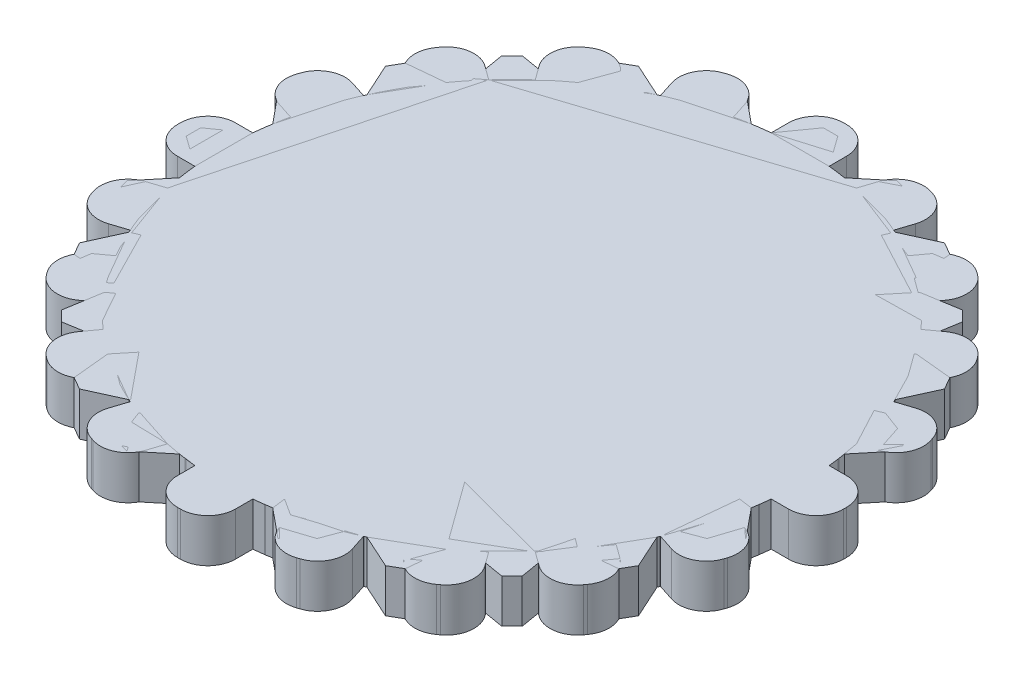
SolidWorks part; units mm, degrees
ref_plane "Front Plane" through (0, 0, 0) normal (0, 0, 1) x (1, 0, 0)
ref_plane "Top Plane" through (0, 0, 0) normal (0, 1, 0) x (1, 0, 0)
ref_plane "Right Plane" through (0, 0, 0) normal (1, 0, 0) x (0, 0, -1)
sketch "Sketch1" plane through (0, 0, 0) normal (0, 1, 0) x (1, 0, 0)
  line L111 (-0.5, 14.7462) -> (0.5, 14.7462)
  line L112 (0.5, 14.7462) -> (2, 12.5441)
  line L113 (-0.5, 14.7462) -> (-2, 12.5441)
  line L114 (6.433, 12.8885) -> (6.631, 10.2315)
  line L115 (5.567, 13.3885) -> (6.433, 12.8885)
  line L116 (5.567, 13.3885) -> (3.1669, 12.2315)
  line L117 (10.6423, 8.3132) -> (9.4853, 5.9131)
  line L118 (10.1423, 9.1792) -> (10.6423, 8.3132)
  line L119 (10.1423, 9.1792) -> (7.4853, 9.3772)
  line L120 (12, 2.2462) -> (9.798, 0.7462)
  line L121 (12, 3.2462) -> (12, 2.2462)
  line L122 (12, 3.2462) -> (9.798, 4.7462)
  line L123 (10.1423, -3.6868) -> (7.4853, -3.8849)
  line L124 (10.6423, -2.8208) -> (10.1423, -3.6868)
  line L125 (10.6423, -2.8208) -> (9.4853, -0.4208)
  line L126 (5.567, -7.8961) -> (3.1669, -6.7391)
  line L127 (6.433, -7.3961) -> (5.567, -7.8961)
  line L128 (6.433, -7.3961) -> (6.631, -4.7391)
  line L129 (-0.5, -9.2538) -> (-2, -7.0518)
  line L130 (0.5, -9.2538) -> (-0.5, -9.2538)
  line L131 (0.5, -9.2538) -> (2, -7.0518)
  line L132 (-6.433, -7.3961) -> (-6.631, -4.7391)
  line L133 (-5.567, -7.8961) -> (-6.433, -7.3961)
  line L134 (-5.567, -7.8961) -> (-3.1669, -6.7391)
  line L135 (-10.6423, -2.8208) -> (-9.4853, -0.4208)
  line L136 (-10.1423, -3.6868) -> (-10.6423, -2.8208)
  line L137 (-10.1423, -3.6868) -> (-7.4853, -3.8849)
  line L138 (-12, 3.2462) -> (-9.798, 4.7462)
  line L139 (-12, 2.2462) -> (-12, 3.2462)
  line L140 (-12, 2.2462) -> (-9.798, 0.7462)
  line L141 (-10.1423, 9.1792) -> (-7.4853, 9.3772)
  line L142 (-10.6423, 8.3132) -> (-10.1423, 9.1792)
  line L143 (-10.6423, 8.3132) -> (-9.4853, 5.9131)
  line L144 (-5.567, 13.3885) -> (-3.1669, 12.2315)
  line L145 (-6.433, 12.8885) -> (-5.567, 13.3885)
  line L146 (-6.433, 12.8885) -> (-6.631, 10.2315)
  arc A43 (-2, 12.5441) -> (-3.1669, 12.2315) centre (0, 2.7462) ccw
  arc A44 (-6.631, 10.2315) -> (-7.4853, 9.3772) centre (0, 2.7462) ccw
  arc A45 (-9.4853, 5.9131) -> (-9.798, 4.7462) centre (0, 2.7462) ccw
  arc A46 (-9.798, 0.7462) -> (-9.4853, -0.4208) centre (0, 2.7462) ccw
  arc A47 (-7.4853, -3.8849) -> (-6.631, -4.7391) centre (0, 2.7462) ccw
  arc A48 (-3.1669, -6.7391) -> (-2, -7.0518) centre (0, 2.7462) ccw
  arc A49 (2, -7.0518) -> (3.1669, -6.7391) centre (0, 2.7462) ccw
  arc A50 (6.631, -4.7391) -> (7.4853, -3.8849) centre (0, 2.7462) ccw
  arc A51 (9.4853, -0.4208) -> (9.798, 0.7462) centre (0, 2.7462) ccw
  arc A52 (9.798, 4.7462) -> (9.4853, 5.9131) centre (0, 2.7462) ccw
  arc A53 (7.4853, 9.3772) -> (6.631, 10.2315) centre (0, 2.7462) ccw
  arc A54 (3.1669, 12.2315) -> (2, 12.5441) centre (0, 2.7462) ccw
  point P6 (0, 0)
  point P8 (0, 0)
  point P9 (0, 0)
  point P12 (0, 2.7462)
  point P17 (0, 0)
  point P18 (0, 2.7462)
  point P22 (-2.5, 0.7462)
  point P63 (0, 0)
  point P68 (0, 0)
  point P69 (0, 2.7462)
  point P119 (0, 0)
  dimension "D1" = 20
  dimension "D8" = 12
sketch "Sketch2" plane through (0, 0, 0) normal (0, 1, 0) x (1, 0, 0)
  line L0 (-2, 0) -> (2, 0)
  line L1 (-23, -0.1) -> (-23, 0.1)
  line L2 (-21.1, 2) -> (-19.8997, 2)
  line L3 (-21.1, -2) -> (-19.8997, -2)
  line L4 (-20.6853, 4.6181) -> (-19.5438, 4.2472)
  line L5 (-19.4493, 8.4224) -> (-18.3078, 8.0515)
  line L6 (-21.9052, 7.0123) -> (-21.8434, 7.2025)
  line L7 (-18.2458, 10.7842) -> (-17.2748, 10.0787)
  line L8 (-15.8947, 14.0203) -> (-14.9237, 13.3148)
  line L9 (-18.6662, 13.4382) -> (-18.5486, 13.6)
  line L10 (-14.0203, 15.8947) -> (-13.3148, 14.9237)
  line L11 (-10.7842, 18.2458) -> (-10.0787, 17.2748)
  line L12 (-13.6, 18.5486) -> (-13.4382, 18.6662)
  line L13 (-8.4224, 19.4493) -> (-8.0515, 18.3078)
  line L14 (-4.6181, 20.6853) -> (-4.2472, 19.5438)
  line L15 (-7.2025, 21.8434) -> (-7.0123, 21.9052)
  line L16 (-2, 21.1) -> (-2, 19.8997)
  line L17 (2, 21.1) -> (2, 19.8997)
  line L18 (-0.1, 23) -> (0.1, 23)
  line L19 (4.6181, 20.6853) -> (4.2472, 19.5438)
  line L20 (8.4224, 19.4493) -> (8.0515, 18.3078)
  line L21 (7.0123, 21.9052) -> (7.2025, 21.8434)
  line L22 (10.7842, 18.2458) -> (10.0787, 17.2748)
  line L23 (14.0203, 15.8947) -> (13.3148, 14.9237)
  line L24 (13.4382, 18.6662) -> (13.6, 18.5486)
  line L25 (15.8947, 14.0203) -> (14.9237, 13.3148)
  line L26 (18.2458, 10.7842) -> (17.2748, 10.0787)
  line L27 (18.5486, 13.6) -> (18.6662, 13.4382)
  line L28 (19.4493, 8.4224) -> (18.3078, 8.0515)
  line L29 (20.6853, 4.6181) -> (19.5438, 4.2472)
  line L30 (21.8434, 7.2025) -> (21.9052, 7.0123)
  line L31 (21.1, 2) -> (19.8997, 2)
  line L32 (21.1, -2) -> (19.8997, -2)
  line L33 (23, 0.1) -> (23, -0.1)
  line L34 (20.6853, -4.6181) -> (19.5438, -4.2472)
  line L35 (19.4493, -8.4224) -> (18.3078, -8.0515)
  line L36 (21.9052, -7.0123) -> (21.8434, -7.2025)
  line L37 (18.2458, -10.7842) -> (17.2748, -10.0787)
  line L38 (15.8947, -14.0203) -> (14.9237, -13.3148)
  line L39 (18.6662, -13.4382) -> (18.5486, -13.6)
  line L40 (14.0203, -15.8947) -> (13.3148, -14.9237)
  line L41 (10.7842, -18.2458) -> (10.0787, -17.2748)
  line L42 (13.6, -18.5486) -> (13.4382, -18.6662)
  line L43 (8.4224, -19.4493) -> (8.0515, -18.3078)
  line L44 (4.6181, -20.6853) -> (4.2472, -19.5438)
  line L45 (7.2025, -21.8434) -> (7.0123, -21.9052)
  line L46 (2, -21.1) -> (2, -19.8997)
  line L47 (-2, -21.1) -> (-2, -19.8997)
  line L48 (0.1, -23) -> (-0.1, -23)
  line L49 (-4.6181, -20.6853) -> (-4.2472, -19.5438)
  line L50 (-8.4224, -19.4493) -> (-8.0515, -18.3078)
  line L51 (-7.0123, -21.9052) -> (-7.2025, -21.8434)
  line L52 (-10.7842, -18.2458) -> (-10.0787, -17.2748)
  line L53 (-14.0203, -15.8947) -> (-13.3148, -14.9237)
  line L54 (-13.4382, -18.6662) -> (-13.6, -18.5486)
  line L55 (-15.8947, -14.0203) -> (-14.9237, -13.3148)
  line L56 (-18.2458, -10.7842) -> (-17.2748, -10.0787)
  line L57 (-18.5486, -13.6) -> (-18.6662, -13.4382)
  line L58 (-19.4493, -8.4224) -> (-18.3078, -8.0515)
  line L59 (-20.6853, -4.6181) -> (-19.5438, -4.2472)
  line L60 (-21.8434, -7.2025) -> (-21.9052, -7.0123)
  arc A0 (-18.3078, -8.0515) -> (-17.2748, -10.0787) centre (0, 0) ccw
  arc A1 (-21.1, 2) -> (-23, 0.1) centre (-21.1, 0.1) ccw
  arc A2 (-21.1, -2) -> (-23, -0.1) centre (-21.1, -0.1) cw
  arc A3 (-20.6853, 4.6181) -> (-21.9052, 7.0123) centre (-20.0982, 6.4252) cw
  arc A4 (-19.4493, 8.4224) -> (-21.8434, 7.2025) centre (-20.0364, 6.6154) ccw
  arc A5 (-18.2458, 10.7842) -> (-18.6662, 13.4382) centre (-17.129, 12.3214) cw
  arc A6 (-15.8947, 14.0203) -> (-18.5486, 13.6) centre (-17.0115, 12.4832) ccw
  arc A7 (-14.0203, 15.8947) -> (-13.6, 18.5486) centre (-12.4832, 17.0115) cw
  arc A8 (-10.7842, 18.2458) -> (-13.4382, 18.6662) centre (-12.3214, 17.129) ccw
  arc A9 (-8.4224, 19.4493) -> (-7.2025, 21.8434) centre (-6.6154, 20.0364) cw
  arc A10 (-4.6181, 20.6853) -> (-7.0123, 21.9052) centre (-6.4252, 20.0982) ccw
  arc A11 (-2, 21.1) -> (-0.1, 23) centre (-0.1, 21.1) cw
  arc A12 (2, 21.1) -> (0.1, 23) centre (0.1, 21.1) ccw
  arc A13 (4.6181, 20.6853) -> (7.0123, 21.9052) centre (6.4252, 20.0982) cw
  arc A14 (8.4224, 19.4493) -> (7.2025, 21.8434) centre (6.6154, 20.0364) ccw
  arc A15 (10.7842, 18.2458) -> (13.4382, 18.6662) centre (12.3214, 17.129) cw
  arc A16 (14.0203, 15.8947) -> (13.6, 18.5486) centre (12.4832, 17.0115) ccw
  arc A17 (15.8947, 14.0203) -> (18.5486, 13.6) centre (17.0115, 12.4832) cw
  arc A18 (18.2458, 10.7842) -> (18.6662, 13.4382) centre (17.129, 12.3214) ccw
  arc A19 (19.4493, 8.4224) -> (21.8434, 7.2025) centre (20.0364, 6.6154) cw
  arc A20 (20.6853, 4.6181) -> (21.9052, 7.0123) centre (20.0982, 6.4252) ccw
  arc A21 (21.1, 2) -> (23, 0.1) centre (21.1, 0.1) cw
  arc A22 (21.1, -2) -> (23, -0.1) centre (21.1, -0.1) ccw
  arc A23 (20.6853, -4.6181) -> (21.9052, -7.0123) centre (20.0982, -6.4252) cw
  arc A24 (19.4493, -8.4224) -> (21.8434, -7.2025) centre (20.0364, -6.6154) ccw
  arc A25 (18.2458, -10.7842) -> (18.6662, -13.4382) centre (17.129, -12.3214) cw
  arc A26 (15.8947, -14.0203) -> (18.5486, -13.6) centre (17.0115, -12.4832) ccw
  arc A27 (14.0203, -15.8947) -> (13.6, -18.5486) centre (12.4832, -17.0115) cw
  arc A28 (10.7842, -18.2458) -> (13.4382, -18.6662) centre (12.3214, -17.129) ccw
  arc A29 (8.4224, -19.4493) -> (7.2025, -21.8434) centre (6.6154, -20.0364) cw
  arc A30 (4.6181, -20.6853) -> (7.0123, -21.9052) centre (6.4252, -20.0982) ccw
  arc A31 (2, -21.1) -> (0.1, -23) centre (0.1, -21.1) cw
  arc A32 (-2, -21.1) -> (-0.1, -23) centre (-0.1, -21.1) ccw
  arc A33 (-4.6181, -20.6853) -> (-7.0123, -21.9052) centre (-6.4252, -20.0982) cw
  arc A34 (-8.4224, -19.4493) -> (-7.2025, -21.8434) centre (-6.6154, -20.0364) ccw
  arc A35 (-10.7842, -18.2458) -> (-13.4382, -18.6662) centre (-12.3214, -17.129) cw
  arc A36 (-14.0203, -15.8947) -> (-13.6, -18.5486) centre (-12.4832, -17.0115) ccw
  arc A37 (-15.8947, -14.0203) -> (-18.5486, -13.6) centre (-17.0115, -12.4832) cw
  arc A38 (-18.2458, -10.7842) -> (-18.6662, -13.4382) centre (-17.129, -12.3214) ccw
  arc A39 (-19.4493, -8.4224) -> (-21.8434, -7.2025) centre (-20.0364, -6.6154) cw
  arc A40 (-20.6853, -4.6181) -> (-21.9052, -7.0123) centre (-20.0982, -6.4252) ccw
  arc A41 (-19.8997, -2) -> (-19.5438, -4.2472) centre (0, 0) ccw
  arc A42 (-19.5438, 4.2472) -> (-19.8997, 2) centre (0, 0) ccw
  arc A43 (-17.2748, 10.0787) -> (-18.3078, 8.0515) centre (0, 0) ccw
  arc A44 (-13.3148, 14.9237) -> (-14.9237, 13.3148) centre (0, 0) ccw
  arc A45 (-8.0515, 18.3078) -> (-10.0787, 17.2748) centre (0, 0) ccw
  arc A46 (-2, 19.8997) -> (-4.2472, 19.5438) centre (0, 0) ccw
  arc A47 (4.2472, 19.5438) -> (2, 19.8997) centre (0, 0) ccw
  arc A48 (10.0787, 17.2748) -> (8.0515, 18.3078) centre (0, 0) ccw
  arc A49 (14.9237, 13.3148) -> (13.3148, 14.9237) centre (0, 0) ccw
  arc A50 (18.3078, 8.0515) -> (17.2748, 10.0787) centre (0, 0) ccw
  arc A51 (19.8997, 2) -> (19.5438, 4.2472) centre (0, 0) ccw
  arc A52 (19.5438, -4.2472) -> (19.8997, -2) centre (0, 0) ccw
  arc A53 (17.2748, -10.0787) -> (18.3078, -8.0515) centre (0, 0) ccw
  arc A54 (13.3148, -14.9237) -> (14.9237, -13.3148) centre (0, 0) ccw
  arc A55 (8.0515, -18.3078) -> (10.0787, -17.2748) centre (0, 0) ccw
  arc A56 (2, -19.8997) -> (4.2472, -19.5438) centre (0, 0) ccw
  arc A57 (-10.0787, -17.2748) -> (-8.0515, -18.3078) centre (0, 0) ccw
  arc A58 (-4.2472, -19.5438) -> (-2, -19.8997) centre (0, 0) ccw
  arc A59 (-14.9237, -13.3148) -> (-13.3148, -14.9237) centre (0, 0) ccw
  point P6 (0, 0)
  point P10 (-23, 2)
  point P170 (0, 0)
  dimension "D1" = 40
  dimension "D4" = 1.9
  dimension "D5" = 20
extrude "Boss-Extrude3" add sketch "Sketch2" along normal blind 3 contours L55 A59 L53 A36 L54 A35 L52 A57 L50 A34 L51 A33 L49 A58 L47 A32 L48 A31 L46 A56 L44 A30 L45 A29 L43 A55 L41 A28 L42 A27 L40 A54 L38 A26 L39 A25 L37 A53 L35 A24 L36 A23 L34 A52 L32 A22 L33 A21 region at (-22.3495, 0, 0)
sketch "Sketch3" plane through (0, 0, 0) normal (0, 1, 0) x (1, 0, 0)
  line L0 (-22, 0) -> (22, 0)
  line L1 (22, -0.5) -> (22, 0.5)
  line L2 (22, 0.5) -> (19.8997, 2)
  line L3 (22, -0.5) -> (19.8997, -2)
  line L4 (21.3798, -5.2111) -> (19.7393, -3.2186)
  line L5 (21.121, -6.177) -> (21.3798, -5.2111)
  line L6 (21.121, -6.177) -> (18.704, -7.0823)
  line L7 (19.3026, -10.567) -> (18.2337, -8.2178)
  line L8 (18.8026, -11.433) -> (19.3026, -10.567)
  line L9 (18.8026, -11.433) -> (16.2337, -11.6819)
  line L10 (15.9099, -15.2028) -> (15.4855, -12.657)
  line L11 (15.2028, -15.9099) -> (15.9099, -15.2028)
  line L12 (15.2028, -15.9099) -> (12.657, -15.4855)
  line L13 (11.433, -18.8026) -> (11.6819, -16.2337)
  line L14 (10.567, -19.3026) -> (11.433, -18.8026)
  line L15 (10.567, -19.3026) -> (8.2178, -18.2337)
  line L16 (6.177, -21.121) -> (7.0823, -18.704)
  line L17 (5.2111, -21.3798) -> (6.177, -21.121)
  line L18 (5.2111, -21.3798) -> (3.2186, -19.7393)
  line L19 (0.5, -22) -> (2, -19.8997)
  line L20 (-0.5, -22) -> (0.5, -22)
  line L21 (-0.5, -22) -> (-2, -19.8997)
  line L22 (-5.2111, -21.3798) -> (-3.2186, -19.7393)
  line L23 (-6.177, -21.121) -> (-5.2111, -21.3798)
  line L24 (-6.177, -21.121) -> (-7.0823, -18.704)
  line L25 (-10.567, -19.3026) -> (-8.2178, -18.2337)
  line L26 (-11.433, -18.8026) -> (-10.567, -19.3026)
  line L27 (-11.433, -18.8026) -> (-11.6819, -16.2337)
  line L28 (-15.2028, -15.9099) -> (-12.657, -15.4855)
  line L29 (-15.9099, -15.2028) -> (-15.2028, -15.9099)
  line L30 (-15.9099, -15.2028) -> (-15.4855, -12.657)
  line L31 (-18.8026, -11.433) -> (-16.2337, -11.6819)
  line L32 (-19.3026, -10.567) -> (-18.8026, -11.433)
  line L33 (-19.3026, -10.567) -> (-18.2337, -8.2178)
  line L34 (-21.121, -6.177) -> (-18.704, -7.0823)
  line L35 (-21.3798, -5.2111) -> (-21.121, -6.177)
  line L36 (-21.3798, -5.2111) -> (-19.7393, -3.2186)
  line L37 (-22, -0.5) -> (-19.8997, -2)
  line L38 (-22, 0.5) -> (-22, -0.5)
  line L39 (-22, 0.5) -> (-19.8997, 2)
  line L40 (-21.3798, 5.2111) -> (-19.7393, 3.2186)
  line L41 (-21.121, 6.177) -> (-21.3798, 5.2111)
  line L42 (-21.121, 6.177) -> (-18.704, 7.0823)
  line L43 (-19.3026, 10.567) -> (-18.2337, 8.2178)
  line L44 (-18.8026, 11.433) -> (-19.3026, 10.567)
  line L45 (-18.8026, 11.433) -> (-16.2337, 11.6819)
  line L46 (-15.9099, 15.2028) -> (-15.4855, 12.657)
  line L47 (-15.2028, 15.9099) -> (-15.9099, 15.2028)
  line L48 (-15.2028, 15.9099) -> (-12.657, 15.4855)
  line L49 (-11.433, 18.8026) -> (-11.6819, 16.2337)
  line L50 (-10.567, 19.3026) -> (-11.433, 18.8026)
  line L51 (-10.567, 19.3026) -> (-8.2178, 18.2337)
  line L52 (-6.177, 21.121) -> (-7.0823, 18.704)
  line L53 (-5.2111, 21.3798) -> (-6.177, 21.121)
  line L54 (-5.2111, 21.3798) -> (-3.2186, 19.7393)
  line L55 (-0.5, 22) -> (-2, 19.8997)
  line L56 (0.5, 22) -> (-0.5, 22)
  line L57 (0.5, 22) -> (2, 19.8997)
  line L58 (5.2111, 21.3798) -> (3.2186, 19.7393)
  line L59 (6.177, 21.121) -> (5.2111, 21.3798)
  line L60 (6.177, 21.121) -> (7.0823, 18.704)
  line L61 (10.567, 19.3026) -> (8.2178, 18.2337)
  line L62 (11.433, 18.8026) -> (10.567, 19.3026)
  line L63 (11.433, 18.8026) -> (11.6819, 16.2337)
  line L64 (15.2028, 15.9099) -> (12.657, 15.4855)
  line L65 (15.9099, 15.2028) -> (15.2028, 15.9099)
  line L66 (15.9099, 15.2028) -> (15.4855, 12.657)
  line L67 (18.8026, 11.433) -> (16.2337, 11.6819)
  line L68 (19.3026, 10.567) -> (18.8026, 11.433)
  line L69 (19.3026, 10.567) -> (18.2337, 8.2178)
  line L70 (21.121, 6.177) -> (18.704, 7.0823)
  line L71 (21.3798, 5.2111) -> (21.121, 6.177)
  line L72 (21.3798, 5.2111) -> (19.7393, 3.2186)
  arc A0 (-8.2178, -18.2337) -> (-7.0823, -18.704) centre (0, 0) ccw
  arc A1 (-12.657, -15.4855) -> (-11.6819, -16.2337) centre (0, 0) ccw
  arc A2 (-16.2337, -11.6819) -> (-15.4855, -12.657) centre (0, 0) ccw
  arc A3 (-18.704, -7.0823) -> (-18.2337, -8.2178) centre (0, 0) ccw
  arc A4 (-19.8997, -2) -> (-19.7393, -3.2186) centre (0, 0) ccw
  arc A5 (-19.7393, 3.2186) -> (-19.8997, 2) centre (0, 0) ccw
  arc A6 (-18.2337, 8.2178) -> (-18.704, 7.0823) centre (0, 0) ccw
  arc A7 (-15.4855, 12.657) -> (-16.2337, 11.6819) centre (0, 0) ccw
  arc A8 (-11.6819, 16.2337) -> (-12.657, 15.4855) centre (0, 0) ccw
  arc A9 (-7.0823, 18.704) -> (-8.2178, 18.2337) centre (0, 0) ccw
  arc A10 (-2, 19.8997) -> (-3.2186, 19.7393) centre (0, 0) ccw
  arc A11 (3.2186, 19.7393) -> (2, 19.8997) centre (0, 0) ccw
  arc A12 (8.2178, 18.2337) -> (7.0823, 18.704) centre (0, 0) ccw
  arc A13 (12.657, 15.4855) -> (11.6819, 16.2337) centre (0, 0) ccw
  arc A14 (16.2337, 11.6819) -> (15.4855, 12.657) centre (0, 0) ccw
  arc A15 (18.704, 7.0823) -> (18.2337, 8.2178) centre (0, 0) ccw
  arc A16 (19.8997, 2) -> (19.7393, 3.2186) centre (0, 0) ccw
  arc A17 (19.7393, -3.2186) -> (19.8997, -2) centre (0, 0) ccw
  arc A18 (18.2337, -8.2178) -> (18.704, -7.0823) centre (0, 0) ccw
  arc A19 (-3.2186, -19.7393) -> (-2, -19.8997) centre (0, 0) ccw
  arc A20 (2, -19.8997) -> (3.2186, -19.7393) centre (0, 0) ccw
  arc A21 (7.0823, -18.704) -> (8.2178, -18.2337) centre (0, 0) ccw
  arc A22 (11.6819, -16.2337) -> (12.657, -15.4855) centre (0, 0) ccw
  arc A23 (15.4855, -12.657) -> (16.2337, -11.6819) centre (0, 0) ccw
  point P6 (0, 0)
  point P7 (0, -12.952)
  point P8 (-6.2727, 0)
  point P9 (11.4668, 0)
  point P10 (0, 0)
  point P108 (0, 0)
  dimension "D1" = 40
  dimension "D2" = 22
  dimension "D3" = 2
  dimension "D4" = 24
extrude "Boss-Extrude5" add sketch "Sketch3" along normal blind 3 separate body contours L2 A16 L72 L71 L70 A15 L69 L68 L67 A14 L66 L65 L64 A13 L63 L62 L61 A12 L60 L59 L58 A11 L57 L56 L55 A10 L54 L53 L52 A9 L51 L50 L49 A8 L48 L47 L46 A7 L45 L44 L43 A6 L42 L41 L40 A5 L39 L38 L0 L1 | L10 A23 L9 L8 L7 A18 L6 L5 L4 A17 L3 L1 L0 L38 L37 A4 L36 L35 L34 A3 L33 L32 L31 A2 L30 L29 L28 A1 L27 L26 L25 A0 L24 L23 L22 A19 L21 L20 L19 A20 L18 L17 L16 A21 L15 L14 L13 A22 L12 L11 region at (0, 0, -8.8989) region at (0, 0, 8.8989)
extrude "Boss-Extrude6" add sketch "Sketch1" along normal blind 3 separate body
sketch "Sketch4" plane through (0, 3, 0) normal (0, 1, 0) x (1, 0, 0)
  circle A0 centre (0, 0) radius 6.25
  dimension "D1" = 12.5
extrude "Cut-Extrude1" cut sketch "Sketch4" against normal blind 10
